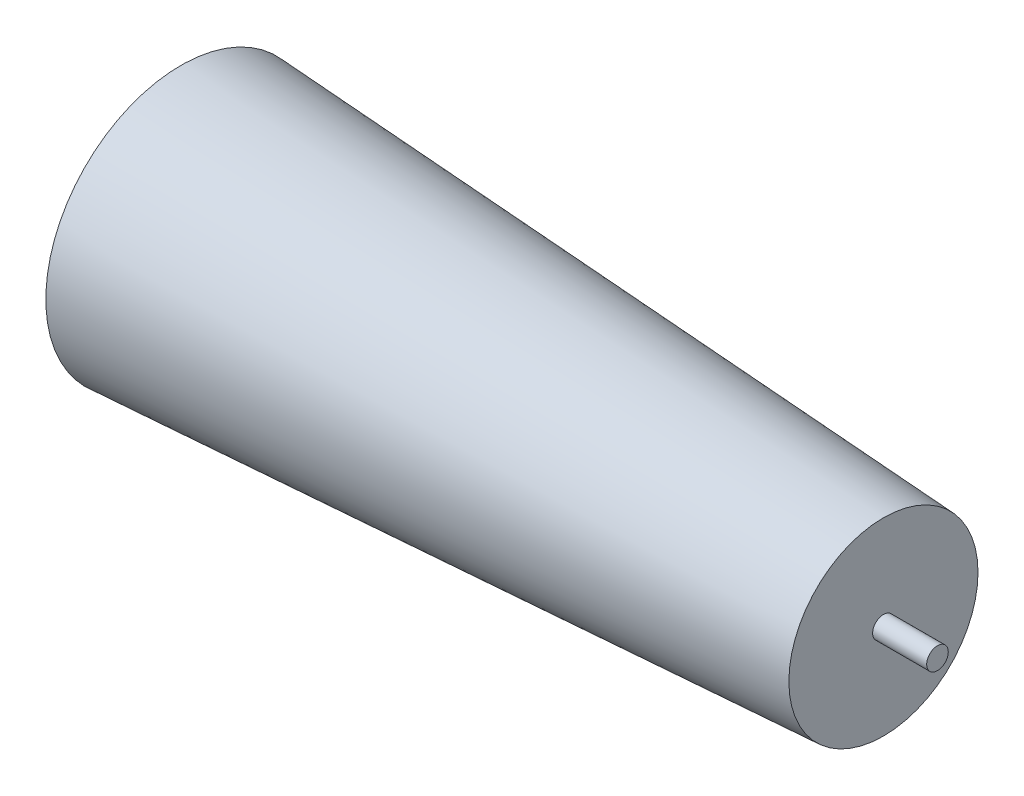
SolidWorks part; units mm, degrees
ref_plane "Front Plane" through (0, 0, 0) normal (0, 0, 1) x (1, 0, 0)
ref_plane "Top Plane" through (0, 0, 0) normal (0, 1, 0) x (1, 0, 0)
ref_plane "Right Plane" through (0, 0, 0) normal (1, 0, 0) x (0, 0, -1)
sketch "Sketch1" plane through (0, 0, 0) normal (1, 0, 0) x (0, 0, -1)
  circle A0 centre (0, 0) radius 50
  dimension "D1" = 100
ref_plane "Plane1" through (260, 0, 0) normal (1, 0, 0) x (0, 0, -1)
sketch "Sketch2" plane through (260, 0, 0) normal (1, 0, 0) x (0, 0, -1)
  circle A0 centre (0, 0) radius 35
  dimension "D1" = 70
loft "Loft1" add profiles "Sketch1", "Sketch2" connector at (0, -15.469, 47.5469) connector at (260, -14.9818, 31.6314)
sketch "Sketch3" plane through (260, 0, 0) normal (1, 0, 0) x (0, 0, -1)
  circle A0 centre (0, 0) radius 4
  dimension "D1" = 8
extrude "Boss-Extrude1" add sketch "Sketch3" along normal blind 20 and the other way blind 280
